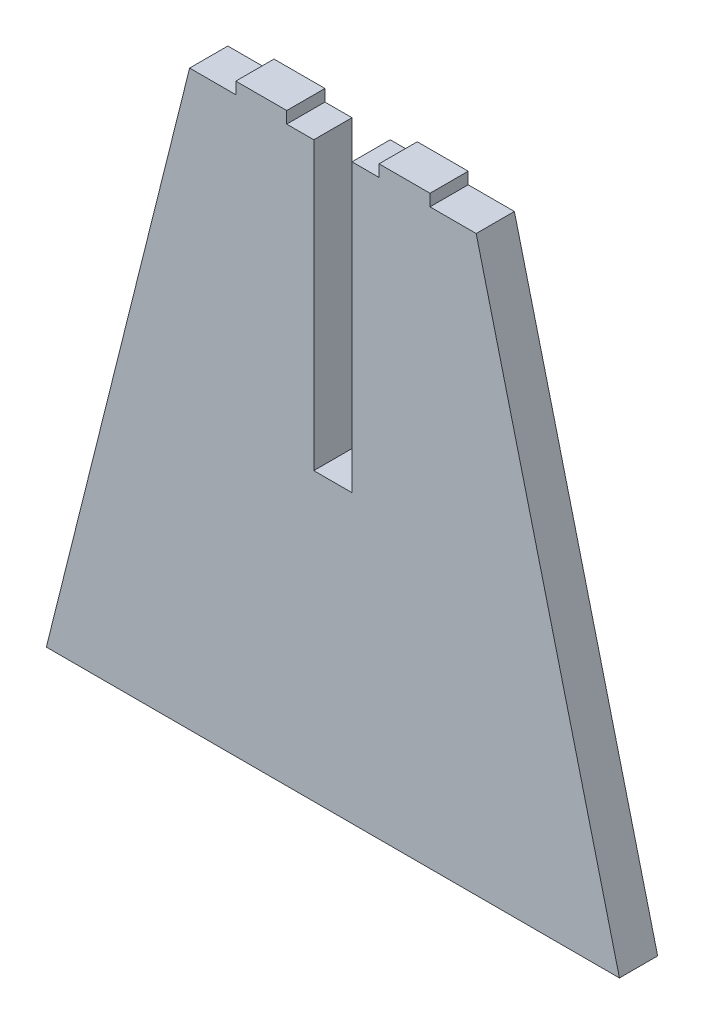
SolidWorks part; units mm, degrees
ref_plane "Front Plane" through (0, 0, 0) normal (0, 0, 1) x (1, 0, 0)
ref_plane "Top Plane" through (0, 0, 0) normal (0, 1, 0) x (1, 0, 0)
ref_plane "Right Plane" through (0, 0, 0) normal (1, 0, 0) x (0, 0, -1)
sketch "Sketch1" plane through (0, 0, 0) normal (0, 0, 1) x (1, 0, 0)
  line L0 (114.8638, 0) -> (0, 0) construction
  line L1 (0, 0) -> (-135.1751, 0) construction
  line L2 (-135.1751, 0) -> (-135.5253, -0.5253) construction
  line L3 (0, 0) -> (0, 108.3852) construction
  line L4 (0, -110.4864) -> (0, 0) construction
  line L5 (45, 15.634) -> (-45, 15.634)
  line L6 (-45, 15.634) -> (-22.5, 105.634)
  line L7 (-22.5, 105.634) -> (-15.25, 105.634)
  line L8 (22.5, 105.634) -> (45, 15.634)
  line L9 (11.25, 108.0853) -> (11.25, 102.0719) construction
  line L10 (-11.25, 108.0853) -> (-11.25, 101.1596) construction
  line L11 (-7.25, 107.4856) -> (-15.25, 107.4856)
  line L13 (7.25, 105.634) -> (7.25, 107.4856)
  line L14 (7.25, 107.4856) -> (15.25, 107.4856)
  line L15 (15.25, 105.634) -> (15.25, 107.4856)
  line L16 (7.25, 60.634) -> (-11.25, 60.634) construction
  line L17 (3.6524, 83.134) -> (-8.6945, 83.134) construction
  line L18 (-15.25, 105.634) -> (-15.25, 107.4856)
  line L20 (-7.25, 105.634) -> (-7.25, 107.4856)
  line L21 (-7.25, 105.634) -> (-3, 105.634)
  line L22 (15.25, 105.634) -> (22.5, 105.634)
  line L23 (3, 105.634) -> (7.25, 105.634)
  line L25 (-3, 105.634) -> (-3, 60.634)
  line L26 (-3, 60.634) -> (3, 60.634)
  line L27 (3, 105.634) -> (3, 60.634)
  point P15 (11.25, 105.634)
  point P28 (0, 83.134)
  dimension "D1" = 90
  dimension "D2" = 45
  dimension "D3" = 90
  dimension "D4" = 22.5
  dimension "D5" = 22.5
  dimension "D6" = 11.25
  dimension "D7" = 11.25
  dimension "D8" = 4
  dimension "D9" = 4
  dimension "D10" = 45
  dimension "D11" = 22.5
  dimension "D12" = 6
extrude "Boss-Extrude1" add sketch "Sketch1" along normal blind 6
